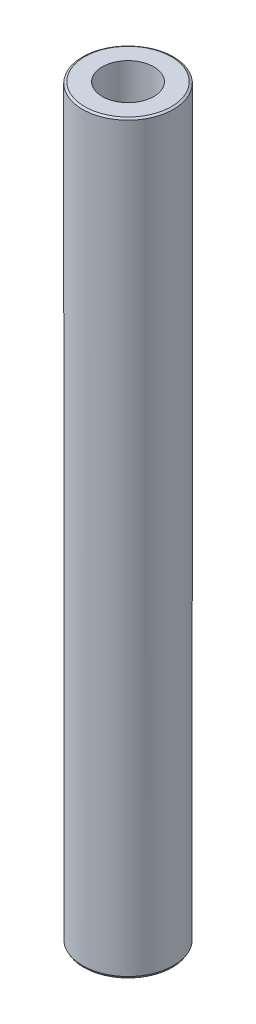
SolidWorks part; units mm, degrees
ref_plane "Front Plane" through (0, 0, 0) normal (0, 0, 1) x (1, 0, 0)
ref_plane "Top Plane" through (0, 0, 0) normal (0, 1, 0) x (1, 0, 0)
ref_plane "Right Plane" through (0, 0, 0) normal (1, 0, 0) x (0, 0, -1)
sketch "Sketch1" plane through (0, 0, 0) normal (0, 1, 0) x (1, 0, 0)
  circle A0 centre (0, 0) radius 35
  dimension "SHAFT_OD" = 70
extrude "Boss-Extrude1" add sketch "Sketch1" along normal blind 573.3421
sketch "Sketch2" plane through (0, 0, 0) normal (0, 1, 0) x (1, 0, 0)
  circle A0 centre (0, 0) radius 19.8361
  dimension "BORE_D" = 39.6722
extrude "Cut-Extrude1" cut sketch "Sketch2" along normal through all
chamfer "Chamfer1" distance 0.9562 angle 60 2 edges at (0, 573.3421, 35) (0, 0, 35) first distance on face at (0, 573.3421, 35) first distance on face at (0, 0, 19.8361)
